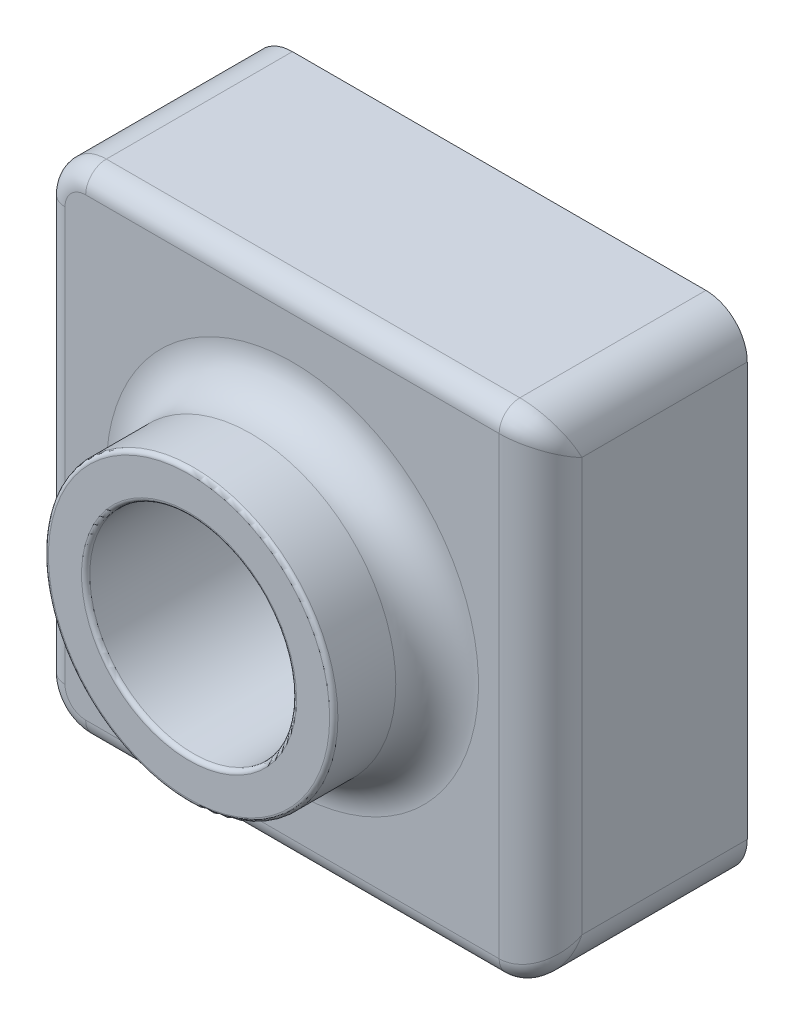
SolidWorks part; units mm, degrees
ref_plane "Front Plane" through (0, 0, 0) normal (0, 0, 1) x (1, 0, 0)
ref_plane "Top Plane" through (0, 0, 0) normal (0, 1, 0) x (1, 0, 0)
ref_plane "Right Plane" through (0, 0, 0) normal (1, 0, 0) x (0, 0, -1)
sketch "Sketch4" plane through (0, 0, 0) normal (0, 0, 1) x (1, 0, 0)
  line L1 (0, 0) -> (120, 0)
  line L2 (0, 0) -> (0, 120)
  line L3 (0, 120) -> (120, 120)
  line L4 (120, 0) -> (120, 120)
  dimension "D1" = 120
  dimension "D2" = 120
extrude "Boss-Extrude2" add sketch "Sketch4" along normal blind 50
sketch "Sketch5" plane through (0, 0, 50) normal (0, 0, 1) x (1, 0, 0)
  line L0 (0, 120) -> (0, 0) construction
  line L1 (120, 120) -> (0, 120) construction
  circle A0 centre (60, 60) radius 35
  dimension "D1" = 70
  dimension "D2" = 60
  dimension "D3" = 60
extrude "Boss-Extrude3" add sketch "Sketch5" along normal blind 25
sketch "Sketch11" plane through (0, 0, 75) normal (0, 0, 1) x (1, 0, 0)
  circle A0 centre (60, 60) radius 25
extrude "Cut-Extrude2" cut sketch "Sketch11" against normal through all
fillet "Fillet1" radius 5 3 edges at (60, 120, 50) (0, 60, 50) (60, 0, 50)
fillet "Fillet2" radius 1 2 edges at (85, 60, 75) (95, 60, 75)
fillet "Fillet3" radius 10 10 edges at (120, 60, 50) (95, 60, 50) (0, 120, 22.5) (0, 0, 22.5) (120, 120, 22.5) (120, 0, 22.5) (1.4645, 118.5355, 48.5355) (120, 118.5355, 48.5355) (1.4645, 1.4645, 48.5355) (120, 1.4645, 48.5355)
shell "Shell1" thickness 2 removed face at (85, 60, 0)
